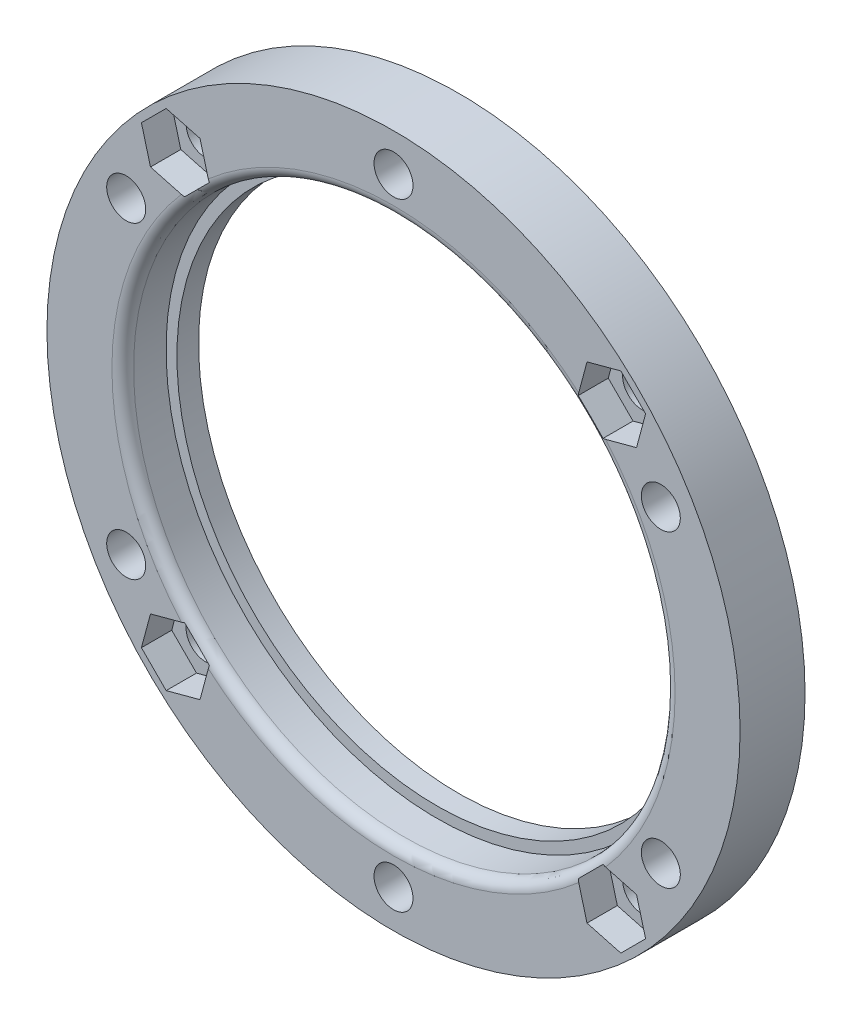
SolidWorks part; units mm, degrees
ref_plane "前视基准面" through (0, 0, 0) normal (0, 0, 1) x (1, 0, 0)
ref_plane "上视基准面" through (0, 0, 0) normal (0, 1, 0) x (1, 0, 0)
ref_plane "右视基准面" through (0, 0, 0) normal (1, 0, 0) x (0, 0, -1)
other "Configuration Table"
sketch "草图1" plane through (0, 0, 0) normal (0, 0, 1) x (1, 0, 0)
  circle A0 centre (0, 0) radius 24
  circle A1 centre (0, 0) radius 32
  dimension "D1" = 48
  dimension "D2" = 64
extrude "凸台-拉伸1" add sketch "草图1" along normal blind 2
sketch "草图2" plane through (0, 0, 2) normal (0, 0, 1) x (1, 0, 0)
  circle A0 centre (0, 0) radius 25
  circle A1 centre (0, 0) radius 32 construction
  circle A2 centre (0, 0) radius 32
  dimension "D1" = 50
extrude "凸台-拉伸2" add sketch "草图2" along normal blind 4
sketch "草图3" plane through (0, 0, 6) normal (0, 0, 1) x (1, 0, 0)
  circle A0 centre (0, 0) radius 28.5 construction
  circle A1 centre (0, 28.5) radius 1.8
  circle A2 centre (24.6817, 14.25) radius 1.8
  circle A3 centre (24.6817, -14.25) radius 1.8
  circle A4 centre (0, -28.5) radius 1.8
  circle A5 centre (-24.6817, -14.25) radius 1.8
  circle A6 centre (-24.6817, 14.25) radius 1.8
  point P17 (0, 0)
  dimension "D1" = 57
  dimension "D2" = 3.6
  dimension "D3" = 6
extrude "切除-拉伸1" cut sketch "草图3" against normal through all
sketch "草图5" plane through (0, 0, 6) normal (0, 0, 1) x (1, 0, 0)
  line L0 (0, 0) -> (-40.7926, 0) construction
  line L1 (0, 0) -> (-33.2914, 33.2914) construction
  line L2 (-17.8664, 22.4387) -> (-22.4387, 17.8664) construction
  line L3 (-17.8664, 22.4387) -> (-20.9893, 23.2755)
  line L4 (-20.9893, 23.2755) -> (-23.2755, 20.9893)
  line L5 (-23.2755, 20.9893) -> (-22.4387, 17.8664)
  line L6 (-22.4387, 17.8664) -> (-19.3157, 17.0295)
  line L7 (-19.3157, 17.0295) -> (-17.0295, 19.3157)
  line L8 (-17.0295, 19.3157) -> (-17.8664, 22.4387)
  line L9 (22.4387, 17.8664) -> (23.2755, 20.9893)
  line L10 (23.2755, 20.9893) -> (20.9893, 23.2755)
  line L11 (20.9893, 23.2755) -> (17.8664, 22.4387)
  line L12 (17.8664, 22.4387) -> (17.0295, 19.3157)
  line L13 (17.0295, 19.3157) -> (19.3157, 17.0295)
  line L14 (19.3157, 17.0295) -> (22.4387, 17.8664)
  line L15 (22.4387, 17.8664) -> (17.8664, 22.4387) construction
  line L16 (17.8664, -22.4387) -> (20.9893, -23.2755)
  line L17 (20.9893, -23.2755) -> (23.2755, -20.9893)
  line L18 (23.2755, -20.9893) -> (22.4387, -17.8664)
  line L19 (22.4387, -17.8664) -> (19.3157, -17.0295)
  line L20 (19.3157, -17.0295) -> (17.0295, -19.3157)
  line L21 (17.0295, -19.3157) -> (17.8664, -22.4387)
  line L22 (17.8664, -22.4387) -> (22.4387, -17.8664) construction
  line L23 (-22.4387, -17.8664) -> (-23.2755, -20.9893)
  line L24 (-23.2755, -20.9893) -> (-20.9893, -23.2755)
  line L25 (-20.9893, -23.2755) -> (-17.8664, -22.4387)
  line L26 (-17.8664, -22.4387) -> (-17.0295, -19.3157)
  line L27 (-17.0295, -19.3157) -> (-19.3157, -17.0295)
  line L28 (-19.3157, -17.0295) -> (-22.4387, -17.8664)
  line L29 (-22.4387, -17.8664) -> (-17.8664, -22.4387) construction
  circle A0 centre (0, 0) radius 28.5 construction
  circle A1 centre (-20.1525, 20.1525) radius 2.8 construction
  circle A2 centre (20.1525, 20.1525) radius 2.8 construction
  circle A3 centre (20.1525, -20.1525) radius 2.8 construction
  circle A4 centre (-20.1525, -20.1525) radius 2.8 construction
  point P41 (0, 0)
  dimension "D1" = 45
  dimension "D2" = 5.6
  dimension "D3" = 4
extrude "切除-拉伸2" cut sketch "草图5" against normal blind 2.8
sketch "草图6" plane through (0, 0, 3.2) normal (0, 0, 1) x (1, 0, 0)
  line L0 (-22.4387, 17.8664) -> (-17.8664, 22.4387) construction
  line L1 (-20.9893, 23.2755) -> (-19.3157, 17.0295) construction
  circle A0 centre (-20.1525, 20.1525) radius 1.8
  circle A1 centre (20.1525, 20.1525) radius 1.8
  circle A2 centre (20.1525, -20.1525) radius 1.8
  circle A3 centre (-20.1525, -20.1525) radius 1.8
  point P19 (0, 0)
  dimension "D1" = 3.6
  dimension "D2" = 4
extrude "切除-拉伸3" cut sketch "草图6" against normal through all
sketch "草图7" plane through (0, 0, 0) normal (0, 0, -1) x (-1, 0, 0)
  line L0 (-3.2332, 28.5) -> (3.2332, 28.5) construction
  line L1 (3.2332, 28.5) -> (1.6166, 31.3)
  line L2 (1.6166, 31.3) -> (-1.6166, 31.3)
  line L3 (-1.6166, 31.3) -> (-3.2332, 28.5)
  line L4 (-3.2332, 28.5) -> (-1.6166, 25.7)
  line L5 (-1.6166, 25.7) -> (1.6166, 25.7)
  line L6 (1.6166, 25.7) -> (3.2332, 28.5)
  line L7 (26.2983, 11.45) -> (27.9149, 14.25)
  line L8 (27.9149, 14.25) -> (26.2983, 17.05)
  line L9 (26.2983, 17.05) -> (23.0651, 17.05)
  line L10 (23.0651, 17.05) -> (21.4486, 14.25)
  line L11 (21.4486, 14.25) -> (23.0651, 11.45)
  line L12 (23.0651, 11.45) -> (26.2983, 11.45)
  line L13 (23.0651, 17.05) -> (26.2983, 11.45) construction
  line L14 (23.0651, -17.05) -> (26.2983, -17.05)
  line L15 (26.2983, -17.05) -> (27.9149, -14.25)
  line L16 (27.9149, -14.25) -> (26.2983, -11.45)
  line L17 (26.2983, -11.45) -> (23.0651, -11.45)
  line L18 (23.0651, -11.45) -> (21.4486, -14.25)
  line L19 (21.4486, -14.25) -> (23.0651, -17.05)
  line L20 (26.2983, -11.45) -> (23.0651, -17.05) construction
  line L21 (-3.2332, -28.5) -> (-1.6166, -31.3)
  line L22 (-1.6166, -31.3) -> (1.6166, -31.3)
  line L23 (1.6166, -31.3) -> (3.2332, -28.5)
  line L24 (3.2332, -28.5) -> (1.6166, -25.7)
  line L25 (1.6166, -25.7) -> (-1.6166, -25.7)
  line L26 (-1.6166, -25.7) -> (-3.2332, -28.5)
  line L27 (3.2332, -28.5) -> (-3.2332, -28.5) construction
  line L28 (-26.2983, -11.45) -> (-27.9149, -14.25)
  line L29 (-27.9149, -14.25) -> (-26.2983, -17.05)
  line L30 (-26.2983, -17.05) -> (-23.0651, -17.05)
  line L31 (-23.0651, -17.05) -> (-21.4486, -14.25)
  line L32 (-21.4486, -14.25) -> (-23.0651, -11.45)
  line L33 (-23.0651, -11.45) -> (-26.2983, -11.45)
  line L34 (-23.0651, -17.05) -> (-26.2983, -11.45) construction
  line L35 (-23.0651, 17.05) -> (-26.2983, 17.05)
  line L36 (-26.2983, 17.05) -> (-27.9149, 14.25)
  line L37 (-27.9149, 14.25) -> (-26.2983, 11.45)
  line L38 (-26.2983, 11.45) -> (-23.0651, 11.45)
  line L39 (-23.0651, 11.45) -> (-21.4486, 14.25)
  line L40 (-21.4486, 14.25) -> (-23.0651, 17.05)
  line L41 (-26.2983, 11.45) -> (-23.0651, 17.05) construction
  circle A0 centre (0, 0) radius 28.5 construction
  circle A1 centre (0, 28.5) radius 2.8 construction
  circle A2 centre (24.6817, 14.25) radius 2.8 construction
  circle A3 centre (24.6817, -14.25) radius 2.8 construction
  circle A4 centre (0, -28.5) radius 2.8 construction
  circle A5 centre (-24.6817, -14.25) radius 2.8 construction
  circle A6 centre (-24.6817, 14.25) radius 2.8 construction
  point P54 (0, 0)
  dimension "D1" = 5.6
  dimension "D2" = 6
extrude "切除-拉伸4" cut sketch "草图7" against normal blind 2.8
fillet "圆角1" radius 1 1 edges at (25, 0, 6)
